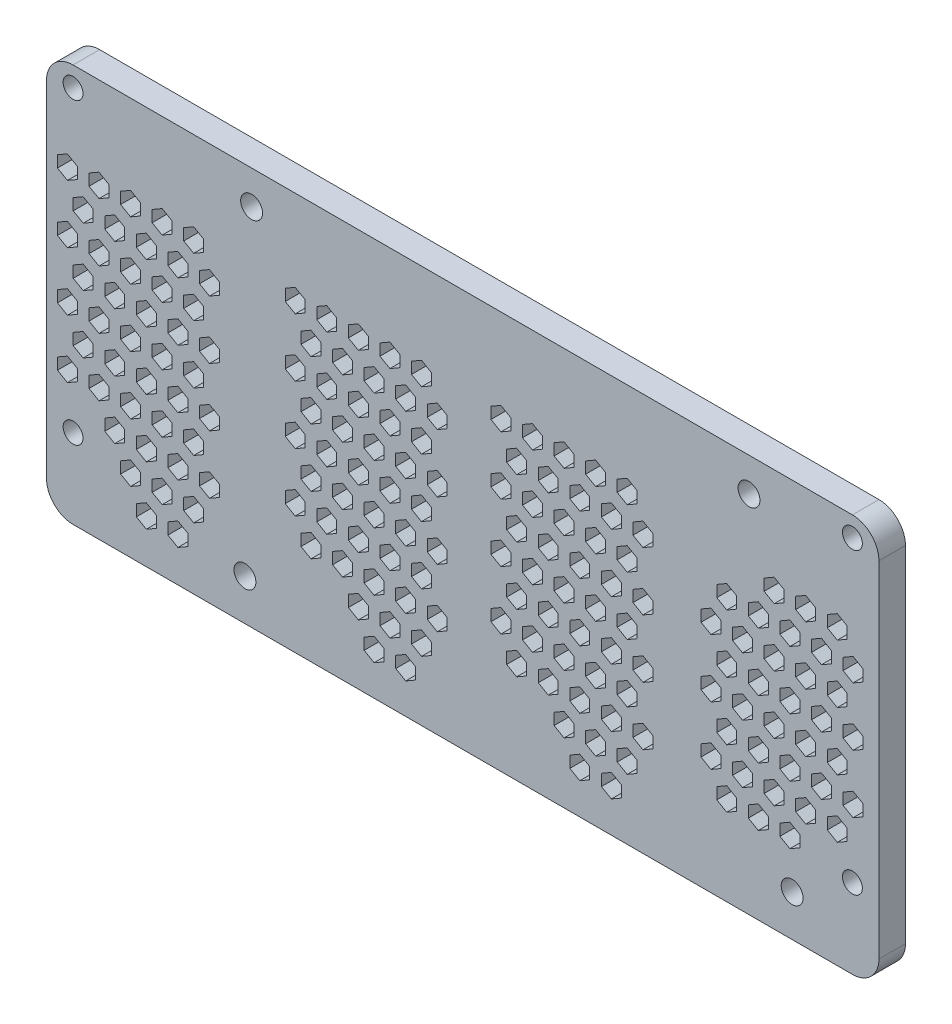
SolidWorks part; units mm, degrees
ref_plane "Front Plane" through (0, 0, 0) normal (0, 0, 1) x (1, 0, 0)
ref_plane "Top Plane" through (0, 0, 0) normal (0, 1, 0) x (1, 0, 0)
ref_plane "Right Plane" through (0, 0, 0) normal (1, 0, 0) x (0, 0, -1)
sketch "Sketch1" plane through (0, 0, 0) normal (0, 0, 1) x (1, 0, 0)
  line L1 (-44, 25.5882) -> (73.5, 25.5882)
  line L2 (-48, 21.5882) -> (-48, -30.4118)
  line L3 (-44, -34.4118) -> (73.5, -34.4118)
  line L4 (77.5, 21.5882) -> (77.5, -30.4118)
  line L10 (-44.8542, 13.5468) -> (-46.3542, 12.6808)
  line L11 (-46.3542, 12.6808) -> (-46.3542, 10.9488)
  line L12 (-46.3542, 10.9488) -> (-44.8542, 10.0827)
  line L13 (-44.8542, 10.0827) -> (-43.3542, 10.9488)
  line L14 (-43.3542, 10.9488) -> (-43.3542, 12.6808)
  line L15 (-43.3542, 12.6808) -> (-44.8542, 13.5468)
  line L17 (-42.4786, 9.1449) -> (-43.9786, 8.2789)
  line L18 (-43.9786, 8.2789) -> (-43.9786, 6.5468)
  line L19 (-43.9786, 6.5468) -> (-42.4786, 5.6808)
  line L20 (-42.4786, 5.6808) -> (-40.9786, 6.5468)
  line L21 (-40.9786, 6.5468) -> (-40.9786, 8.2789)
  line L22 (-40.9786, 8.2789) -> (-42.4786, 9.1449)
  line L23 (-40.0942, 13.5468) -> (-41.5942, 12.6808)
  line L24 (-41.5942, 12.6808) -> (-41.5942, 10.9488)
  line L25 (-41.5942, 10.9488) -> (-40.0942, 10.0827)
  line L26 (-40.0942, 10.0827) -> (-38.5942, 10.9488)
  line L27 (-38.5942, 10.9488) -> (-38.5942, 12.6808)
  line L28 (-38.5942, 12.6808) -> (-40.0942, 13.5468)
  line L29 (-37.7186, 9.1449) -> (-39.2186, 8.2789)
  line L30 (-39.2186, 8.2789) -> (-39.2186, 6.5468)
  line L31 (-39.2186, 6.5468) -> (-37.7186, 5.6808)
  line L32 (-37.7186, 5.6808) -> (-36.2186, 6.5468)
  line L33 (-36.2186, 6.5468) -> (-36.2186, 8.2789)
  line L34 (-36.2186, 8.2789) -> (-37.7186, 9.1449)
  line L35 (-35.3342, 13.5468) -> (-36.8342, 12.6808)
  line L36 (-36.8342, 12.6808) -> (-36.8342, 10.9488)
  line L37 (-36.8342, 10.9488) -> (-35.3342, 10.0827)
  line L38 (-35.3342, 10.0827) -> (-33.8342, 10.9488)
  line L39 (-33.8342, 10.9488) -> (-33.8342, 12.6808)
  line L40 (-33.8342, 12.6808) -> (-35.3342, 13.5468)
  line L41 (-32.9586, 9.1449) -> (-34.4586, 8.2789)
  line L42 (-34.4586, 8.2789) -> (-34.4586, 6.5468)
  line L43 (-34.4586, 6.5468) -> (-32.9586, 5.6808)
  line L44 (-32.9586, 5.6808) -> (-31.4586, 6.5468)
  line L45 (-31.4586, 6.5468) -> (-31.4586, 8.2789)
  line L46 (-31.4586, 8.2789) -> (-32.9586, 9.1449)
  line L47 (-30.5742, 13.5468) -> (-32.0742, 12.6808)
  line L48 (-32.0742, 12.6808) -> (-32.0742, 10.9488)
  line L49 (-32.0742, 10.9488) -> (-30.5742, 10.0827)
  line L50 (-30.5742, 10.0827) -> (-29.0742, 10.9488)
  line L51 (-29.0742, 10.9488) -> (-29.0742, 12.6808)
  line L52 (-29.0742, 12.6808) -> (-30.5742, 13.5468)
  line L53 (-28.1986, 9.1449) -> (-29.6986, 8.2789)
  line L54 (-29.6986, 8.2789) -> (-29.6986, 6.5468)
  line L55 (-29.6986, 6.5468) -> (-28.1986, 5.6808)
  line L56 (-28.1986, 5.6808) -> (-26.6986, 6.5468)
  line L57 (-26.6986, 6.5468) -> (-26.6986, 8.2789)
  line L58 (-26.6986, 8.2789) -> (-28.1986, 9.1449)
  line L59 (-25.8142, 13.5468) -> (-27.3142, 12.6808)
  line L60 (-27.3142, 12.6808) -> (-27.3142, 10.9488)
  line L61 (-27.3142, 10.9488) -> (-25.8142, 10.0827)
  line L62 (-25.8142, 10.0827) -> (-24.3142, 10.9488)
  line L63 (-24.3142, 10.9488) -> (-24.3142, 12.6808)
  line L64 (-24.3142, 12.6808) -> (-25.8142, 13.5468)
  line L65 (-23.4386, 9.1449) -> (-24.9386, 8.2789)
  line L66 (-24.9386, 8.2789) -> (-24.9386, 6.5468)
  line L67 (-24.9386, 6.5468) -> (-23.4386, 5.6808)
  line L68 (-23.4386, 5.6808) -> (-21.9386, 6.5468)
  line L69 (-21.9386, 6.5468) -> (-21.9386, 8.2789)
  line L70 (-21.9386, 8.2789) -> (-23.4386, 9.1449)
  line L71 (-40.0942, 4.7468) -> (-41.5942, 3.8808)
  line L72 (-41.5942, 3.8808) -> (-41.5942, 2.1488)
  line L73 (-41.5942, 2.1488) -> (-40.0942, 1.2827)
  line L74 (-40.0942, 1.2827) -> (-38.5942, 2.1488)
  line L75 (-38.5942, 2.1488) -> (-38.5942, 3.8808)
  line L76 (-38.5942, 3.8808) -> (-40.0942, 4.7468)
  line L77 (-37.7186, 0.3449) -> (-39.2186, -0.5211)
  line L78 (-39.2186, -0.5211) -> (-39.2186, -2.2532)
  line L79 (-39.2186, -2.2532) -> (-37.7186, -3.1192)
  line L80 (-37.7186, -3.1192) -> (-36.2186, -2.2532)
  line L81 (-36.2186, -2.2532) -> (-36.2186, -0.5211)
  line L82 (-36.2186, -0.5211) -> (-37.7186, 0.3449)
  line L83 (-35.3342, 4.7468) -> (-36.8342, 3.8808)
  line L84 (-36.8342, 3.8808) -> (-36.8342, 2.1488)
  line L85 (-36.8342, 2.1488) -> (-35.3342, 1.2827)
  line L86 (-35.3342, 1.2827) -> (-33.8342, 2.1488)
  line L87 (-33.8342, 2.1488) -> (-33.8342, 3.8808)
  line L88 (-33.8342, 3.8808) -> (-35.3342, 4.7468)
  line L89 (-32.9586, 0.3449) -> (-34.4586, -0.5211)
  line L90 (-34.4586, -0.5211) -> (-34.4586, -2.2532)
  line L91 (-34.4586, -2.2532) -> (-32.9586, -3.1192)
  line L92 (-32.9586, -3.1192) -> (-31.4586, -2.2532)
  line L93 (-31.4586, -2.2532) -> (-31.4586, -0.5211)
  line L94 (-31.4586, -0.5211) -> (-32.9586, 0.3449)
  line L95 (-30.5742, 4.7468) -> (-32.0742, 3.8808)
  line L96 (-32.0742, 3.8808) -> (-32.0742, 2.1488)
  line L97 (-32.0742, 2.1488) -> (-30.5742, 1.2827)
  line L98 (-30.5742, 1.2827) -> (-29.0742, 2.1488)
  line L99 (-29.0742, 2.1488) -> (-29.0742, 3.8808)
  line L100 (-29.0742, 3.8808) -> (-30.5742, 4.7468)
  line L101 (-28.1986, 0.3449) -> (-29.6986, -0.5211)
  line L102 (-29.6986, -0.5211) -> (-29.6986, -2.2532)
  line L103 (-29.6986, -2.2532) -> (-28.1986, -3.1192)
  line L104 (-28.1986, -3.1192) -> (-26.6986, -2.2532)
  line L105 (-26.6986, -2.2532) -> (-26.6986, -0.5211)
  line L106 (-26.6986, -0.5211) -> (-28.1986, 0.3449)
  line L107 (-25.8142, 4.7468) -> (-27.3142, 3.8808)
  line L108 (-27.3142, 3.8808) -> (-27.3142, 2.1488)
  line L109 (-27.3142, 2.1488) -> (-25.8142, 1.2827)
  line L110 (-25.8142, 1.2827) -> (-24.3142, 2.1488)
  line L111 (-24.3142, 2.1488) -> (-24.3142, 3.8808)
  line L112 (-24.3142, 3.8808) -> (-25.8142, 4.7468)
  line L113 (-23.4386, 0.3449) -> (-24.9386, -0.5211)
  line L114 (-24.9386, -0.5211) -> (-24.9386, -2.2532)
  line L115 (-24.9386, -2.2532) -> (-23.4386, -3.1192)
  line L116 (-23.4386, -3.1192) -> (-21.9386, -2.2532)
  line L117 (-21.9386, -2.2532) -> (-21.9386, -0.5211)
  line L118 (-21.9386, -0.5211) -> (-23.4386, 0.3449)
  line L119 (-40.0942, -4.0532) -> (-41.5942, -4.9192)
  line L120 (-41.5942, -4.9192) -> (-41.5942, -6.6512)
  line L121 (-41.5942, -6.6512) -> (-40.0942, -7.5173)
  line L122 (-40.0942, -7.5173) -> (-38.5942, -6.6512)
  line L123 (-38.5942, -6.6512) -> (-38.5942, -4.9192)
  line L124 (-38.5942, -4.9192) -> (-40.0942, -4.0532)
  line L125 (-37.7186, -8.4551) -> (-39.2186, -9.3211)
  line L126 (-39.2186, -9.3211) -> (-39.2186, -11.0532)
  line L127 (-39.2186, -11.0532) -> (-37.7186, -11.9192)
  line L128 (-37.7186, -11.9192) -> (-36.2186, -11.0532)
  line L129 (-36.2186, -11.0532) -> (-36.2186, -9.3211)
  line L130 (-36.2186, -9.3211) -> (-37.7186, -8.4551)
  line L131 (-35.3342, -4.0532) -> (-36.8342, -4.9192)
  line L132 (-36.8342, -4.9192) -> (-36.8342, -6.6512)
  line L133 (-36.8342, -6.6512) -> (-35.3342, -7.5173)
  line L134 (-35.3342, -7.5173) -> (-33.8342, -6.6512)
  line L135 (-33.8342, -6.6512) -> (-33.8342, -4.9192)
  line L136 (-33.8342, -4.9192) -> (-35.3342, -4.0532)
  line L137 (-32.9586, -8.4551) -> (-34.4586, -9.3211)
  line L138 (-34.4586, -9.3211) -> (-34.4586, -11.0532)
  line L139 (-34.4586, -11.0532) -> (-32.9586, -11.9192)
  line L140 (-32.9586, -11.9192) -> (-31.4586, -11.0532)
  line L141 (-31.4586, -11.0532) -> (-31.4586, -9.3211)
  line L142 (-31.4586, -9.3211) -> (-32.9586, -8.4551)
  line L143 (-30.5742, -4.0532) -> (-32.0742, -4.9192)
  line L144 (-32.0742, -4.9192) -> (-32.0742, -6.6512)
  line L145 (-32.0742, -6.6512) -> (-30.5742, -7.5173)
  line L146 (-30.5742, -7.5173) -> (-29.0742, -6.6512)
  line L147 (-29.0742, -6.6512) -> (-29.0742, -4.9192)
  line L148 (-29.0742, -4.9192) -> (-30.5742, -4.0532)
  line L149 (-28.1986, -8.4551) -> (-29.6986, -9.3211)
  line L150 (-29.6986, -9.3211) -> (-29.6986, -11.0532)
  line L151 (-29.6986, -11.0532) -> (-28.1986, -11.9192)
  line L152 (-28.1986, -11.9192) -> (-26.6986, -11.0532)
  line L153 (-26.6986, -11.0532) -> (-26.6986, -9.3211)
  line L154 (-26.6986, -9.3211) -> (-28.1986, -8.4551)
  line L155 (-25.8142, -4.0532) -> (-27.3142, -4.9192)
  line L156 (-27.3142, -4.9192) -> (-27.3142, -6.6512)
  line L157 (-27.3142, -6.6512) -> (-25.8142, -7.5173)
  line L158 (-25.8142, -7.5173) -> (-24.3142, -6.6512)
  line L159 (-24.3142, -6.6512) -> (-24.3142, -4.9192)
  line L160 (-24.3142, -4.9192) -> (-25.8142, -4.0532)
  line L161 (-23.4386, -8.4551) -> (-24.9386, -9.3211)
  line L162 (-24.9386, -9.3211) -> (-24.9386, -11.0532)
  line L163 (-24.9386, -11.0532) -> (-23.4386, -11.9192)
  line L164 (-23.4386, -11.9192) -> (-21.9386, -11.0532)
  line L165 (-21.9386, -11.0532) -> (-21.9386, -9.3211)
  line L166 (-21.9386, -9.3211) -> (-23.4386, -8.4551)
  line L167 (-40.0942, -12.8532) -> (-41.5942, -13.7192)
  line L168 (-41.5942, -13.7192) -> (-41.5942, -15.4512)
  line L169 (-41.5942, -15.4512) -> (-40.0942, -16.3173)
  line L170 (-40.0942, -16.3173) -> (-38.5942, -15.4512)
  line L171 (-38.5942, -15.4512) -> (-38.5942, -13.7192)
  line L172 (-38.5942, -13.7192) -> (-40.0942, -12.8532)
  line L173 (-37.7186, -17.2551) -> (-39.2186, -18.1211)
  line L174 (-39.2186, -18.1211) -> (-39.2186, -19.8532)
  line L175 (-39.2186, -19.8532) -> (-37.7186, -20.7192)
  line L176 (-37.7186, -20.7192) -> (-36.2186, -19.8532)
  line L177 (-36.2186, -19.8532) -> (-36.2186, -18.1211)
  line L178 (-36.2186, -18.1211) -> (-37.7186, -17.2551)
  line L179 (-35.3342, -12.8532) -> (-36.8342, -13.7192)
  line L180 (-36.8342, -13.7192) -> (-36.8342, -15.4512)
  line L181 (-36.8342, -15.4512) -> (-35.3342, -16.3173)
  line L182 (-35.3342, -16.3173) -> (-33.8342, -15.4512)
  line L183 (-33.8342, -15.4512) -> (-33.8342, -13.7192)
  line L184 (-33.8342, -13.7192) -> (-35.3342, -12.8532)
  line L185 (-32.9586, -17.2551) -> (-34.4586, -18.1211)
  line L186 (-34.4586, -18.1211) -> (-34.4586, -19.8532)
  line L187 (-34.4586, -19.8532) -> (-32.9586, -20.7192)
  line L188 (-32.9586, -20.7192) -> (-31.4586, -19.8532)
  line L189 (-31.4586, -19.8532) -> (-31.4586, -18.1211)
  line L190 (-31.4586, -18.1211) -> (-32.9586, -17.2551)
  line L191 (-30.5742, -12.8532) -> (-32.0742, -13.7192)
  line L192 (-32.0742, -13.7192) -> (-32.0742, -15.4512)
  line L193 (-32.0742, -15.4512) -> (-30.5742, -16.3173)
  line L194 (-30.5742, -16.3173) -> (-29.0742, -15.4512)
  line L195 (-29.0742, -15.4512) -> (-29.0742, -13.7192)
  line L196 (-29.0742, -13.7192) -> (-30.5742, -12.8532)
  line L197 (-28.1986, -17.2551) -> (-29.6986, -18.1211)
  line L198 (-29.6986, -18.1211) -> (-29.6986, -19.8532)
  line L199 (-29.6986, -19.8532) -> (-28.1986, -20.7192)
  line L200 (-28.1986, -20.7192) -> (-26.6986, -19.8532)
  line L201 (-26.6986, -19.8532) -> (-26.6986, -18.1211)
  line L202 (-26.6986, -18.1211) -> (-28.1986, -17.2551)
  line L203 (-25.8142, -12.8532) -> (-27.3142, -13.7192)
  line L204 (-27.3142, -13.7192) -> (-27.3142, -15.4512)
  line L205 (-27.3142, -15.4512) -> (-25.8142, -16.3173)
  line L206 (-25.8142, -16.3173) -> (-24.3142, -15.4512)
  line L207 (-24.3142, -15.4512) -> (-24.3142, -13.7192)
  line L208 (-24.3142, -13.7192) -> (-25.8142, -12.8532)
  line L209 (-23.4386, -17.2551) -> (-24.9386, -18.1211)
  line L210 (-24.9386, -18.1211) -> (-24.9386, -19.8532)
  line L211 (-24.9386, -19.8532) -> (-23.4386, -20.7192)
  line L212 (-23.4386, -20.7192) -> (-21.9386, -19.8532)
  line L213 (-21.9386, -19.8532) -> (-21.9386, -18.1211)
  line L214 (-21.9386, -18.1211) -> (-23.4386, -17.2551)
  line L227 (-35.3342, -21.6532) -> (-36.8342, -22.5192)
  line L228 (-36.8342, -22.5192) -> (-36.8342, -24.2512)
  line L229 (-36.8342, -24.2512) -> (-35.3342, -25.1173)
  line L230 (-35.3342, -25.1173) -> (-33.8342, -24.2512)
  line L231 (-33.8342, -24.2512) -> (-33.8342, -22.5192)
  line L232 (-33.8342, -22.5192) -> (-35.3342, -21.6532)
  line L233 (-32.9586, -26.0551) -> (-34.4586, -26.9211)
  line L234 (-34.4586, -26.9211) -> (-34.4586, -28.6532)
  line L235 (-34.4586, -28.6532) -> (-32.9586, -29.5192)
  line L236 (-32.9586, -29.5192) -> (-31.4586, -28.6532)
  line L237 (-31.4586, -28.6532) -> (-31.4586, -26.9211)
  line L238 (-31.4586, -26.9211) -> (-32.9586, -26.0551)
  line L239 (-30.5742, -21.6532) -> (-32.0742, -22.5192)
  line L240 (-32.0742, -22.5192) -> (-32.0742, -24.2512)
  line L241 (-32.0742, -24.2512) -> (-30.5742, -25.1173)
  line L242 (-30.5742, -25.1173) -> (-29.0742, -24.2512)
  line L243 (-29.0742, -24.2512) -> (-29.0742, -22.5192)
  line L244 (-29.0742, -22.5192) -> (-30.5742, -21.6532)
  line L245 (-28.1986, -26.0551) -> (-29.6986, -26.9211)
  line L246 (-29.6986, -26.9211) -> (-29.6986, -28.6532)
  line L247 (-29.6986, -28.6532) -> (-28.1986, -29.5192)
  line L248 (-28.1986, -29.5192) -> (-26.6986, -28.6532)
  line L249 (-26.6986, -28.6532) -> (-26.6986, -26.9211)
  line L250 (-26.6986, -26.9211) -> (-28.1986, -26.0551)
  line L251 (-25.8142, -21.6532) -> (-27.3142, -22.5192)
  line L252 (-27.3142, -22.5192) -> (-27.3142, -24.2512)
  line L253 (-27.3142, -24.2512) -> (-25.8142, -25.1173)
  line L254 (-25.8142, -25.1173) -> (-24.3142, -24.2512)
  line L255 (-24.3142, -24.2512) -> (-24.3142, -22.5192)
  line L256 (-24.3142, -22.5192) -> (-25.8142, -21.6532)
  line L263 (-44.8542, 4.7468) -> (-46.3542, 3.8808)
  line L264 (-46.3542, 3.8808) -> (-46.3542, 2.1488)
  line L265 (-46.3542, 2.1488) -> (-44.8542, 1.2827)
  line L266 (-44.8542, 1.2827) -> (-43.3542, 2.1488)
  line L267 (-43.3542, 2.1488) -> (-43.3542, 3.8808)
  line L268 (-43.3542, 3.8808) -> (-44.8542, 4.7468)
  line L269 (-42.4786, 0.3449) -> (-43.9786, -0.5211)
  line L270 (-43.9786, -0.5211) -> (-43.9786, -2.2532)
  line L271 (-43.9786, -2.2532) -> (-42.4786, -3.1192)
  line L272 (-42.4786, -3.1192) -> (-40.9786, -2.2532)
  line L273 (-40.9786, -2.2532) -> (-40.9786, -0.5211)
  line L274 (-40.9786, -0.5211) -> (-42.4786, 0.3449)
  line L275 (-44.8542, -4.0532) -> (-46.3542, -4.9192)
  line L276 (-46.3542, -4.9192) -> (-46.3542, -6.6512)
  line L277 (-46.3542, -6.6512) -> (-44.8542, -7.5173)
  line L278 (-44.8542, -7.5173) -> (-43.3542, -6.6512)
  line L279 (-43.3542, -6.6512) -> (-43.3542, -4.9192)
  line L280 (-43.3542, -4.9192) -> (-44.8542, -4.0532)
  line L281 (-42.4786, -8.4551) -> (-43.9786, -9.3211)
  line L282 (-43.9786, -9.3211) -> (-43.9786, -11.0532)
  line L283 (-43.9786, -11.0532) -> (-42.4786, -11.9192)
  line L284 (-42.4786, -11.9192) -> (-40.9786, -11.0532)
  line L285 (-40.9786, -11.0532) -> (-40.9786, -9.3211)
  line L286 (-40.9786, -9.3211) -> (-42.4786, -8.4551)
  line L287 (-44.8542, -12.8532) -> (-46.3542, -13.7192)
  line L288 (-46.3542, -13.7192) -> (-46.3542, -15.4512)
  line L289 (-46.3542, -15.4512) -> (-44.8542, -16.3173)
  line L290 (-44.8542, -16.3173) -> (-43.3542, -15.4512)
  line L291 (-43.3542, -15.4512) -> (-43.3542, -13.7192)
  line L292 (-43.3542, -13.7192) -> (-44.8542, -12.8532)
  line L311 (-44.8542, -21.6532) -> (-46.3542, -22.5192) [skipped]
  line L312 (-46.3542, -22.5192) -> (-46.3542, -24.2512) [skipped]
  line L313 (-46.3542, -24.2512) -> (-44.8542, -25.1173) [skipped]
  line L314 (-44.8542, -25.1173) -> (-43.3542, -24.2512) [skipped]
  line L315 (-43.3542, -24.2512) -> (-43.3542, -22.5192) [skipped]
  line L316 (-43.3542, -22.5192) -> (-44.8542, -21.6532) [skipped]
  line L317 (-42.4786, -26.0551) -> (-43.9786, -26.9211) [skipped]
  line L318 (-43.9786, -26.9211) -> (-43.9786, -28.6532) [skipped]
  line L319 (-43.9786, -28.6532) -> (-42.4786, -29.5192) [skipped]
  line L320 (-42.4786, -29.5192) -> (-40.9786, -28.6532) [skipped]
  line L321 (-40.9786, -28.6532) -> (-40.9786, -26.9211) [skipped]
  line L322 (-40.9786, -26.9211) -> (-42.4786, -26.0551) [skipped]
  line L323 (-37.7186, -26.0551) -> (-39.2186, -26.9211) [skipped]
  line L324 (-39.2186, -26.9211) -> (-39.2186, -28.6532) [skipped]
  line L325 (-39.2186, -28.6532) -> (-37.7186, -29.5192) [skipped]
  line L326 (-37.7186, -29.5192) -> (-36.2186, -28.6532) [skipped]
  line L327 (-36.2186, -28.6532) -> (-36.2186, -26.9211) [skipped]
  line L328 (-36.2186, -26.9211) -> (-37.7186, -26.0551) [skipped]
  line L329 (-40.0942, -21.6532) -> (-41.5942, -22.5192) [skipped]
  line L330 (-41.5942, -22.5192) -> (-41.5942, -24.2512) [skipped]
  line L331 (-41.5942, -24.2512) -> (-40.0942, -25.1173) [skipped]
  line L332 (-40.0942, -25.1173) -> (-38.5942, -24.2512) [skipped]
  line L333 (-38.5942, -24.2512) -> (-38.5942, -22.5192) [skipped]
  line L334 (-38.5942, -22.5192) -> (-40.0942, -21.6532) [skipped]
  line L335 (-23.4386, -26.0551) -> (-24.9386, -26.9211) [skipped]
  line L336 (-24.9386, -26.9211) -> (-24.9386, -28.6532) [skipped]
  line L337 (-24.9386, -28.6532) -> (-23.4386, -29.5192) [skipped]
  line L338 (-23.4386, -29.5192) -> (-21.9386, -28.6532) [skipped]
  line L339 (-21.9386, -28.6532) -> (-21.9386, -26.9211) [skipped]
  line L340 (-21.9386, -26.9211) -> (-23.4386, -26.0551) [skipped]
  line L347 (54.5534, 7.152) -> (53.0534, 6.286)
  line L348 (53.0534, 6.286) -> (53.0534, 4.554)
  line L349 (53.0534, 4.554) -> (54.5534, 3.6879)
  line L350 (54.5534, 3.6879) -> (56.0534, 4.554)
  line L351 (56.0534, 4.554) -> (56.0534, 6.286)
  line L352 (56.0534, 6.286) -> (54.5534, 7.152)
  line L359 (59.3134, 7.152) -> (57.8134, 6.286)
  line L360 (57.8134, 6.286) -> (57.8134, 4.554)
  line L361 (57.8134, 4.554) -> (59.3134, 3.6879)
  line L362 (59.3134, 3.6879) -> (60.8134, 4.554)
  line L363 (60.8134, 4.554) -> (60.8134, 6.286)
  line L364 (60.8134, 6.286) -> (59.3134, 7.152)
  line L365 (61.6978, 11.554) -> (60.1978, 10.6879)
  line L366 (60.1978, 10.6879) -> (60.1978, 8.9559)
  line L367 (60.1978, 8.9559) -> (61.6978, 8.0899)
  line L368 (61.6978, 8.0899) -> (63.1978, 8.9559)
  line L369 (63.1978, 8.9559) -> (63.1978, 10.6879)
  line L370 (63.1978, 10.6879) -> (61.6978, 11.554)
  line L371 (64.0734, 7.152) -> (62.5734, 6.286)
  line L372 (62.5734, 6.286) -> (62.5734, 4.554)
  line L373 (62.5734, 4.554) -> (64.0734, 3.6879)
  line L374 (64.0734, 3.6879) -> (65.5734, 4.554)
  line L375 (65.5734, 4.554) -> (65.5734, 6.286)
  line L376 (65.5734, 6.286) -> (64.0734, 7.152)
  line L377 (66.4578, 11.554) -> (64.9578, 10.6879)
  line L378 (64.9578, 10.6879) -> (64.9578, 8.9559)
  line L379 (64.9578, 8.9559) -> (66.4578, 8.0899)
  line L380 (66.4578, 8.0899) -> (67.9578, 8.9559)
  line L381 (67.9578, 8.9559) -> (67.9578, 10.6879)
  line L382 (67.9578, 10.6879) -> (66.4578, 11.554)
  line L383 (68.8334, 7.152) -> (67.3334, 6.286)
  line L384 (67.3334, 6.286) -> (67.3334, 4.554)
  line L385 (67.3334, 4.554) -> (68.8334, 3.6879)
  line L386 (68.8334, 3.6879) -> (70.3334, 4.554)
  line L387 (70.3334, 4.554) -> (70.3334, 6.286)
  line L388 (70.3334, 6.286) -> (68.8334, 7.152)
  line L389 (71.2178, 11.554) -> (69.7178, 10.6879)
  line L390 (69.7178, 10.6879) -> (69.7178, 8.9559)
  line L391 (69.7178, 8.9559) -> (71.2178, 8.0899)
  line L392 (71.2178, 8.0899) -> (72.7178, 8.9559)
  line L393 (72.7178, 8.9559) -> (72.7178, 10.6879)
  line L394 (72.7178, 10.6879) -> (71.2178, 11.554)
  line L395 (73.5934, 7.152) -> (72.0934, 6.286)
  line L396 (72.0934, 6.286) -> (72.0934, 4.554)
  line L397 (72.0934, 4.554) -> (73.5934, 3.6879)
  line L398 (73.5934, 3.6879) -> (75.0934, 4.554)
  line L399 (75.0934, 4.554) -> (75.0934, 6.286)
  line L400 (75.0934, 6.286) -> (73.5934, 7.152)
  line L401 (56.9378, 2.754) -> (55.4378, 1.8879)
  line L402 (55.4378, 1.8879) -> (55.4378, 0.1559)
  line L403 (55.4378, 0.1559) -> (56.9378, -0.7101)
  line L404 (56.9378, -0.7101) -> (58.4378, 0.1559)
  line L405 (58.4378, 0.1559) -> (58.4378, 1.8879)
  line L406 (58.4378, 1.8879) -> (56.9378, 2.754)
  line L407 (59.3134, -1.648) -> (57.8134, -2.514)
  line L408 (57.8134, -2.514) -> (57.8134, -4.246)
  line L409 (57.8134, -4.246) -> (59.3134, -5.1121)
  line L410 (59.3134, -5.1121) -> (60.8134, -4.246)
  line L411 (60.8134, -4.246) -> (60.8134, -2.514)
  line L412 (60.8134, -2.514) -> (59.3134, -1.648)
  line L413 (61.6978, 2.754) -> (60.1978, 1.8879)
  line L414 (60.1978, 1.8879) -> (60.1978, 0.1559)
  line L415 (60.1978, 0.1559) -> (61.6978, -0.7101)
  line L416 (61.6978, -0.7101) -> (63.1978, 0.1559)
  line L417 (63.1978, 0.1559) -> (63.1978, 1.8879)
  line L418 (63.1978, 1.8879) -> (61.6978, 2.754)
  line L419 (64.0734, -1.648) -> (62.5734, -2.514)
  line L420 (62.5734, -2.514) -> (62.5734, -4.246)
  line L421 (62.5734, -4.246) -> (64.0734, -5.1121)
  line L422 (64.0734, -5.1121) -> (65.5734, -4.246)
  line L423 (65.5734, -4.246) -> (65.5734, -2.514)
  line L424 (65.5734, -2.514) -> (64.0734, -1.648)
  line L425 (66.4578, 2.754) -> (64.9578, 1.8879)
  line L426 (64.9578, 1.8879) -> (64.9578, 0.1559)
  line L427 (64.9578, 0.1559) -> (66.4578, -0.7101)
  line L428 (66.4578, -0.7101) -> (67.9578, 0.1559)
  line L429 (67.9578, 0.1559) -> (67.9578, 1.8879)
  line L430 (67.9578, 1.8879) -> (66.4578, 2.754)
  line L431 (68.8334, -1.648) -> (67.3334, -2.514)
  line L432 (67.3334, -2.514) -> (67.3334, -4.246)
  line L433 (67.3334, -4.246) -> (68.8334, -5.1121)
  line L434 (68.8334, -5.1121) -> (70.3334, -4.246)
  line L435 (70.3334, -4.246) -> (70.3334, -2.514)
  line L436 (70.3334, -2.514) -> (68.8334, -1.648)
  line L437 (71.2178, 2.754) -> (69.7178, 1.8879)
  line L438 (69.7178, 1.8879) -> (69.7178, 0.1559)
  line L439 (69.7178, 0.1559) -> (71.2178, -0.7101)
  line L440 (71.2178, -0.7101) -> (72.7178, 0.1559)
  line L441 (72.7178, 0.1559) -> (72.7178, 1.8879)
  line L442 (72.7178, 1.8879) -> (71.2178, 2.754)
  line L443 (73.5934, -1.648) -> (72.0934, -2.514)
  line L444 (72.0934, -2.514) -> (72.0934, -4.246)
  line L445 (72.0934, -4.246) -> (73.5934, -5.1121)
  line L446 (73.5934, -5.1121) -> (75.0934, -4.246)
  line L447 (75.0934, -4.246) -> (75.0934, -2.514)
  line L448 (75.0934, -2.514) -> (73.5934, -1.648)
  line L449 (56.9378, -6.046) -> (55.4378, -6.9121)
  line L450 (55.4378, -6.9121) -> (55.4378, -8.6441)
  line L451 (55.4378, -8.6441) -> (56.9378, -9.5101)
  line L452 (56.9378, -9.5101) -> (58.4378, -8.6441)
  line L453 (58.4378, -8.6441) -> (58.4378, -6.9121)
  line L454 (58.4378, -6.9121) -> (56.9378, -6.046)
  line L455 (59.3134, -10.448) -> (57.8134, -11.314)
  line L456 (57.8134, -11.314) -> (57.8134, -13.046)
  line L457 (57.8134, -13.046) -> (59.3134, -13.9121)
  line L458 (59.3134, -13.9121) -> (60.8134, -13.046)
  line L459 (60.8134, -13.046) -> (60.8134, -11.314)
  line L460 (60.8134, -11.314) -> (59.3134, -10.448)
  line L461 (61.6978, -6.046) -> (60.1978, -6.9121)
  line L462 (60.1978, -6.9121) -> (60.1978, -8.6441)
  line L463 (60.1978, -8.6441) -> (61.6978, -9.5101)
  line L464 (61.6978, -9.5101) -> (63.1978, -8.6441)
  line L465 (63.1978, -8.6441) -> (63.1978, -6.9121)
  line L466 (63.1978, -6.9121) -> (61.6978, -6.046)
  line L467 (64.0734, -10.448) -> (62.5734, -11.314)
  line L468 (62.5734, -11.314) -> (62.5734, -13.046)
  line L469 (62.5734, -13.046) -> (64.0734, -13.9121)
  line L470 (64.0734, -13.9121) -> (65.5734, -13.046)
  line L471 (65.5734, -13.046) -> (65.5734, -11.314)
  line L472 (65.5734, -11.314) -> (64.0734, -10.448)
  line L473 (66.4578, -6.046) -> (64.9578, -6.9121)
  line L474 (64.9578, -6.9121) -> (64.9578, -8.6441)
  line L475 (64.9578, -8.6441) -> (66.4578, -9.5101)
  line L476 (66.4578, -9.5101) -> (67.9578, -8.6441)
  line L477 (67.9578, -8.6441) -> (67.9578, -6.9121)
  line L478 (67.9578, -6.9121) -> (66.4578, -6.046)
  line L479 (68.8334, -10.448) -> (67.3334, -11.314)
  line L480 (67.3334, -11.314) -> (67.3334, -13.046)
  line L481 (67.3334, -13.046) -> (68.8334, -13.9121)
  line L482 (68.8334, -13.9121) -> (70.3334, -13.046)
  line L483 (70.3334, -13.046) -> (70.3334, -11.314)
  line L484 (70.3334, -11.314) -> (68.8334, -10.448)
  line L485 (71.2178, -6.046) -> (69.7178, -6.9121)
  line L486 (69.7178, -6.9121) -> (69.7178, -8.6441)
  line L487 (69.7178, -8.6441) -> (71.2178, -9.5101)
  line L488 (71.2178, -9.5101) -> (72.7178, -8.6441)
  line L489 (72.7178, -8.6441) -> (72.7178, -6.9121)
  line L490 (72.7178, -6.9121) -> (71.2178, -6.046)
  line L491 (73.5934, -10.448) -> (72.0934, -11.314)
  line L492 (72.0934, -11.314) -> (72.0934, -13.046)
  line L493 (72.0934, -13.046) -> (73.5934, -13.9121)
  line L494 (73.5934, -13.9121) -> (75.0934, -13.046)
  line L495 (75.0934, -13.046) -> (75.0934, -11.314)
  line L496 (75.0934, -11.314) -> (73.5934, -10.448)
  line L497 (56.9378, -14.846) -> (55.4378, -15.7121)
  line L498 (55.4378, -15.7121) -> (55.4378, -17.4441)
  line L499 (55.4378, -17.4441) -> (56.9378, -18.3101)
  line L500 (56.9378, -18.3101) -> (58.4378, -17.4441)
  line L501 (58.4378, -17.4441) -> (58.4378, -15.7121)
  line L502 (58.4378, -15.7121) -> (56.9378, -14.846)
  line L503 (59.3134, -19.248) -> (57.8134, -20.114)
  line L504 (57.8134, -20.114) -> (57.8134, -21.846)
  line L505 (57.8134, -21.846) -> (59.3134, -22.7121)
  line L506 (59.3134, -22.7121) -> (60.8134, -21.846)
  line L507 (60.8134, -21.846) -> (60.8134, -20.114)
  line L508 (60.8134, -20.114) -> (59.3134, -19.248)
  line L509 (61.6978, -14.846) -> (60.1978, -15.7121)
  line L510 (60.1978, -15.7121) -> (60.1978, -17.4441)
  line L511 (60.1978, -17.4441) -> (61.6978, -18.3101)
  line L512 (61.6978, -18.3101) -> (63.1978, -17.4441)
  line L513 (63.1978, -17.4441) -> (63.1978, -15.7121)
  line L514 (63.1978, -15.7121) -> (61.6978, -14.846)
  line L515 (64.0734, -19.248) -> (62.5734, -20.114)
  line L516 (62.5734, -20.114) -> (62.5734, -21.846)
  line L517 (62.5734, -21.846) -> (64.0734, -22.7121)
  line L518 (64.0734, -22.7121) -> (65.5734, -21.846)
  line L519 (65.5734, -21.846) -> (65.5734, -20.114)
  line L520 (65.5734, -20.114) -> (64.0734, -19.248)
  line L521 (66.4578, -14.846) -> (64.9578, -15.7121)
  line L522 (64.9578, -15.7121) -> (64.9578, -17.4441)
  line L523 (64.9578, -17.4441) -> (66.4578, -18.3101)
  line L524 (66.4578, -18.3101) -> (67.9578, -17.4441)
  line L525 (67.9578, -17.4441) -> (67.9578, -15.7121)
  line L526 (67.9578, -15.7121) -> (66.4578, -14.846)
  line L533 (71.2178, -14.846) -> (69.7178, -15.7121)
  line L534 (69.7178, -15.7121) -> (69.7178, -17.4441)
  line L535 (69.7178, -17.4441) -> (71.2178, -18.3101)
  line L536 (71.2178, -18.3101) -> (72.7178, -17.4441)
  line L537 (72.7178, -17.4441) -> (72.7178, -15.7121)
  line L538 (72.7178, -15.7121) -> (71.2178, -14.846)
  line L575 (52.1778, 2.754) -> (50.6778, 1.8879)
  line L576 (50.6778, 1.8879) -> (50.6778, 0.1559)
  line L577 (50.6778, 0.1559) -> (52.1778, -0.7101)
  line L578 (52.1778, -0.7101) -> (53.6778, 0.1559)
  line L579 (53.6778, 0.1559) -> (53.6778, 1.8879)
  line L580 (53.6778, 1.8879) -> (52.1778, 2.754)
  line L581 (54.5534, -1.648) -> (53.0534, -2.514)
  line L582 (53.0534, -2.514) -> (53.0534, -4.246)
  line L583 (53.0534, -4.246) -> (54.5534, -5.1121)
  line L584 (54.5534, -5.1121) -> (56.0534, -4.246)
  line L585 (56.0534, -4.246) -> (56.0534, -2.514)
  line L586 (56.0534, -2.514) -> (54.5534, -1.648)
  line L587 (52.1778, -6.046) -> (50.6778, -6.9121)
  line L588 (50.6778, -6.9121) -> (50.6778, -8.6441)
  line L589 (50.6778, -8.6441) -> (52.1778, -9.5101)
  line L590 (52.1778, -9.5101) -> (53.6778, -8.6441)
  line L591 (53.6778, -8.6441) -> (53.6778, -6.9121)
  line L592 (53.6778, -6.9121) -> (52.1778, -6.046)
  line L593 (54.5534, -10.448) -> (53.0534, -11.314)
  line L594 (53.0534, -11.314) -> (53.0534, -13.046)
  line L595 (53.0534, -13.046) -> (54.5534, -13.9121)
  line L596 (54.5534, -13.9121) -> (56.0534, -13.046)
  line L597 (56.0534, -13.046) -> (56.0534, -11.314)
  line L598 (56.0534, -11.314) -> (54.5534, -10.448)
  line L599 (52.1778, -14.846) -> (50.6778, -15.7121)
  line L600 (50.6778, -15.7121) -> (50.6778, -17.4441)
  line L601 (50.6778, -17.4441) -> (52.1778, -18.3101)
  line L602 (52.1778, -18.3101) -> (53.6778, -17.4441)
  line L603 (53.6778, -17.4441) -> (53.6778, -15.7121)
  line L604 (53.6778, -15.7121) -> (52.1778, -14.846)
  line L605 (54.5534, -19.248) -> (53.0534, -20.114)
  line L606 (53.0534, -20.114) -> (53.0534, -21.846)
  line L607 (53.0534, -21.846) -> (54.5534, -22.7121)
  line L608 (54.5534, -22.7121) -> (56.0534, -21.846)
  line L609 (56.0534, -21.846) -> (56.0534, -20.114)
  line L610 (56.0534, -20.114) -> (54.5534, -19.248)
  line L611 (-10.5093, 13.2923) -> (-12.0093, 12.4263)
  line L612 (-12.0093, 12.4263) -> (-12.0093, 10.6942)
  line L613 (-12.0093, 10.6942) -> (-10.5093, 9.8282)
  line L614 (-10.5093, 9.8282) -> (-9.0093, 10.6942)
  line L615 (-9.0093, 10.6942) -> (-9.0093, 12.4263)
  line L616 (-9.0093, 12.4263) -> (-10.5093, 13.2923)
  line L617 (-8.1336, 8.8904) -> (-9.6336, 8.0244)
  line L618 (-9.6336, 8.0244) -> (-9.6336, 6.2923)
  line L619 (-9.6336, 6.2923) -> (-8.1336, 5.4263)
  line L620 (-8.1336, 5.4263) -> (-6.6336, 6.2923)
  line L621 (-6.6336, 6.2923) -> (-6.6336, 8.0244)
  line L622 (-6.6336, 8.0244) -> (-8.1336, 8.8904)
  line L623 (-5.7493, 13.2923) -> (-7.2493, 12.4263)
  line L624 (-7.2493, 12.4263) -> (-7.2493, 10.6942)
  line L625 (-7.2493, 10.6942) -> (-5.7493, 9.8282)
  line L626 (-5.7493, 9.8282) -> (-4.2493, 10.6942)
  line L627 (-4.2493, 10.6942) -> (-4.2493, 12.4263)
  line L628 (-4.2493, 12.4263) -> (-5.7493, 13.2923)
  line L629 (-3.3736, 8.8904) -> (-4.8736, 8.0244)
  line L630 (-4.8736, 8.0244) -> (-4.8736, 6.2923)
  line L631 (-4.8736, 6.2923) -> (-3.3736, 5.4263)
  line L632 (-3.3736, 5.4263) -> (-1.8736, 6.2923)
  line L633 (-1.8736, 6.2923) -> (-1.8736, 8.0244)
  line L634 (-1.8736, 8.0244) -> (-3.3736, 8.8904)
  line L635 (-0.9893, 13.2923) -> (-2.4893, 12.4263)
  line L636 (-2.4893, 12.4263) -> (-2.4893, 10.6942)
  line L637 (-2.4893, 10.6942) -> (-0.9893, 9.8282)
  line L638 (-0.9893, 9.8282) -> (0.5107, 10.6942)
  line L639 (0.5107, 10.6942) -> (0.5107, 12.4263)
  line L640 (0.5107, 12.4263) -> (-0.9893, 13.2923)
  line L641 (1.3864, 8.8904) -> (-0.1136, 8.0244)
  line L642 (-0.1136, 8.0244) -> (-0.1136, 6.2923)
  line L643 (-0.1136, 6.2923) -> (1.3864, 5.4263)
  line L644 (1.3864, 5.4263) -> (2.8864, 6.2923)
  line L645 (2.8864, 6.2923) -> (2.8864, 8.0244)
  line L646 (2.8864, 8.0244) -> (1.3864, 8.8904)
  line L647 (3.7707, 13.2923) -> (2.2707, 12.4263)
  line L648 (2.2707, 12.4263) -> (2.2707, 10.6942)
  line L649 (2.2707, 10.6942) -> (3.7707, 9.8282)
  line L650 (3.7707, 9.8282) -> (5.2707, 10.6942)
  line L651 (5.2707, 10.6942) -> (5.2707, 12.4263)
  line L652 (5.2707, 12.4263) -> (3.7707, 13.2923)
  line L653 (6.1464, 8.8904) -> (4.6464, 8.0244)
  line L654 (4.6464, 8.0244) -> (4.6464, 6.2923)
  line L655 (4.6464, 6.2923) -> (6.1464, 5.4263)
  line L656 (6.1464, 5.4263) -> (7.6464, 6.2923)
  line L657 (7.6464, 6.2923) -> (7.6464, 8.0244)
  line L658 (7.6464, 8.0244) -> (6.1464, 8.8904)
  line L659 (8.5307, 13.2923) -> (7.0307, 12.4263)
  line L660 (7.0307, 12.4263) -> (7.0307, 10.6942)
  line L661 (7.0307, 10.6942) -> (8.5307, 9.8282)
  line L662 (8.5307, 9.8282) -> (10.0307, 10.6942)
  line L663 (10.0307, 10.6942) -> (10.0307, 12.4263)
  line L664 (10.0307, 12.4263) -> (8.5307, 13.2923)
  line L665 (10.9064, 8.8904) -> (9.4064, 8.0244)
  line L666 (9.4064, 8.0244) -> (9.4064, 6.2923)
  line L667 (9.4064, 6.2923) -> (10.9064, 5.4263)
  line L668 (10.9064, 5.4263) -> (12.4064, 6.2923)
  line L669 (12.4064, 6.2923) -> (12.4064, 8.0244)
  line L670 (12.4064, 8.0244) -> (10.9064, 8.8904)
  line L671 (-5.7493, 4.4923) -> (-7.2493, 3.6263)
  line L672 (-7.2493, 3.6263) -> (-7.2493, 1.8942)
  line L673 (-7.2493, 1.8942) -> (-5.7493, 1.0282)
  line L674 (-5.7493, 1.0282) -> (-4.2493, 1.8942)
  line L675 (-4.2493, 1.8942) -> (-4.2493, 3.6263)
  line L676 (-4.2493, 3.6263) -> (-5.7493, 4.4923)
  line L677 (-3.3736, 0.0904) -> (-4.8736, -0.7756)
  line L678 (-4.8736, -0.7756) -> (-4.8736, -2.5077)
  line L679 (-4.8736, -2.5077) -> (-3.3736, -3.3737)
  line L680 (-3.3736, -3.3737) -> (-1.8736, -2.5077)
  line L681 (-1.8736, -2.5077) -> (-1.8736, -0.7756)
  line L682 (-1.8736, -0.7756) -> (-3.3736, 0.0904)
  line L683 (-0.9893, 4.4923) -> (-2.4893, 3.6263)
  line L684 (-2.4893, 3.6263) -> (-2.4893, 1.8942)
  line L685 (-2.4893, 1.8942) -> (-0.9893, 1.0282)
  line L686 (-0.9893, 1.0282) -> (0.5107, 1.8942)
  line L687 (0.5107, 1.8942) -> (0.5107, 3.6263)
  line L688 (0.5107, 3.6263) -> (-0.9893, 4.4923)
  line L689 (1.3864, 0.0904) -> (-0.1136, -0.7756)
  line L690 (-0.1136, -0.7756) -> (-0.1136, -2.5077)
  line L691 (-0.1136, -2.5077) -> (1.3864, -3.3737)
  line L692 (1.3864, -3.3737) -> (2.8864, -2.5077)
  line L693 (2.8864, -2.5077) -> (2.8864, -0.7756)
  line L694 (2.8864, -0.7756) -> (1.3864, 0.0904)
  line L695 (3.7707, 4.4923) -> (2.2707, 3.6263)
  line L696 (2.2707, 3.6263) -> (2.2707, 1.8942)
  line L697 (2.2707, 1.8942) -> (3.7707, 1.0282)
  line L698 (3.7707, 1.0282) -> (5.2707, 1.8942)
  line L699 (5.2707, 1.8942) -> (5.2707, 3.6263)
  line L700 (5.2707, 3.6263) -> (3.7707, 4.4923)
  line L701 (6.1464, 0.0904) -> (4.6464, -0.7756)
  line L702 (4.6464, -0.7756) -> (4.6464, -2.5077)
  line L703 (4.6464, -2.5077) -> (6.1464, -3.3737)
  line L704 (6.1464, -3.3737) -> (7.6464, -2.5077)
  line L705 (7.6464, -2.5077) -> (7.6464, -0.7756)
  line L706 (7.6464, -0.7756) -> (6.1464, 0.0904)
  line L707 (8.5307, 4.4923) -> (7.0307, 3.6263)
  line L708 (7.0307, 3.6263) -> (7.0307, 1.8942)
  line L709 (7.0307, 1.8942) -> (8.5307, 1.0282)
  line L710 (8.5307, 1.0282) -> (10.0307, 1.8942)
  line L711 (10.0307, 1.8942) -> (10.0307, 3.6263)
  line L712 (10.0307, 3.6263) -> (8.5307, 4.4923)
  line L713 (10.9064, 0.0904) -> (9.4064, -0.7756)
  line L714 (9.4064, -0.7756) -> (9.4064, -2.5077)
  line L715 (9.4064, -2.5077) -> (10.9064, -3.3737)
  line L716 (10.9064, -3.3737) -> (12.4064, -2.5077)
  line L717 (12.4064, -2.5077) -> (12.4064, -0.7756)
  line L718 (12.4064, -0.7756) -> (10.9064, 0.0904)
  line L719 (-5.7493, -4.3077) -> (-7.2493, -5.1737)
  line L720 (-7.2493, -5.1737) -> (-7.2493, -6.9058)
  line L721 (-7.2493, -6.9058) -> (-5.7493, -7.7718)
  line L722 (-5.7493, -7.7718) -> (-4.2493, -6.9058)
  line L723 (-4.2493, -6.9058) -> (-4.2493, -5.1737)
  line L724 (-4.2493, -5.1737) -> (-5.7493, -4.3077)
  line L725 (-3.3736, -8.7096) -> (-4.8736, -9.5756)
  line L726 (-4.8736, -9.5756) -> (-4.8736, -11.3077)
  line L727 (-4.8736, -11.3077) -> (-3.3736, -12.1737)
  line L728 (-3.3736, -12.1737) -> (-1.8736, -11.3077)
  line L729 (-1.8736, -11.3077) -> (-1.8736, -9.5756)
  line L730 (-1.8736, -9.5756) -> (-3.3736, -8.7096)
  line L731 (-0.9893, -4.3077) -> (-2.4893, -5.1737)
  line L732 (-2.4893, -5.1737) -> (-2.4893, -6.9058)
  line L733 (-2.4893, -6.9058) -> (-0.9893, -7.7718)
  line L734 (-0.9893, -7.7718) -> (0.5107, -6.9058)
  line L735 (0.5107, -6.9058) -> (0.5107, -5.1737)
  line L736 (0.5107, -5.1737) -> (-0.9893, -4.3077)
  line L737 (1.3864, -8.7096) -> (-0.1136, -9.5756)
  line L738 (-0.1136, -9.5756) -> (-0.1136, -11.3077)
  line L739 (-0.1136, -11.3077) -> (1.3864, -12.1737)
  line L740 (1.3864, -12.1737) -> (2.8864, -11.3077)
  line L741 (2.8864, -11.3077) -> (2.8864, -9.5756)
  line L742 (2.8864, -9.5756) -> (1.3864, -8.7096)
  line L743 (3.7707, -4.3077) -> (2.2707, -5.1737)
  line L744 (2.2707, -5.1737) -> (2.2707, -6.9058)
  line L745 (2.2707, -6.9058) -> (3.7707, -7.7718)
  line L746 (3.7707, -7.7718) -> (5.2707, -6.9058)
  line L747 (5.2707, -6.9058) -> (5.2707, -5.1737)
  line L748 (5.2707, -5.1737) -> (3.7707, -4.3077)
  line L749 (6.1464, -8.7096) -> (4.6464, -9.5756)
  line L750 (4.6464, -9.5756) -> (4.6464, -11.3077)
  line L751 (4.6464, -11.3077) -> (6.1464, -12.1737)
  line L752 (6.1464, -12.1737) -> (7.6464, -11.3077)
  line L753 (7.6464, -11.3077) -> (7.6464, -9.5756)
  line L754 (7.6464, -9.5756) -> (6.1464, -8.7096)
  line L755 (8.5307, -4.3077) -> (7.0307, -5.1737)
  line L756 (7.0307, -5.1737) -> (7.0307, -6.9058)
  line L757 (7.0307, -6.9058) -> (8.5307, -7.7718)
  line L758 (8.5307, -7.7718) -> (10.0307, -6.9058)
  line L759 (10.0307, -6.9058) -> (10.0307, -5.1737)
  line L760 (10.0307, -5.1737) -> (8.5307, -4.3077)
  line L761 (10.9064, -8.7096) -> (9.4064, -9.5756)
  line L762 (9.4064, -9.5756) -> (9.4064, -11.3077)
  line L763 (9.4064, -11.3077) -> (10.9064, -12.1737)
  line L764 (10.9064, -12.1737) -> (12.4064, -11.3077)
  line L765 (12.4064, -11.3077) -> (12.4064, -9.5756)
  line L766 (12.4064, -9.5756) -> (10.9064, -8.7096)
  line L767 (-5.7493, -13.1077) -> (-7.2493, -13.9737)
  line L768 (-7.2493, -13.9737) -> (-7.2493, -15.7058)
  line L769 (-7.2493, -15.7058) -> (-5.7493, -16.5718)
  line L770 (-5.7493, -16.5718) -> (-4.2493, -15.7058)
  line L771 (-4.2493, -15.7058) -> (-4.2493, -13.9737)
  line L772 (-4.2493, -13.9737) -> (-5.7493, -13.1077)
  line L773 (-3.3736, -17.5096) -> (-4.8736, -18.3756)
  line L774 (-4.8736, -18.3756) -> (-4.8736, -20.1077)
  line L775 (-4.8736, -20.1077) -> (-3.3736, -20.9737)
  line L776 (-3.3736, -20.9737) -> (-1.8736, -20.1077)
  line L777 (-1.8736, -20.1077) -> (-1.8736, -18.3756)
  line L778 (-1.8736, -18.3756) -> (-3.3736, -17.5096)
  line L779 (-0.9893, -13.1077) -> (-2.4893, -13.9737)
  line L780 (-2.4893, -13.9737) -> (-2.4893, -15.7058)
  line L781 (-2.4893, -15.7058) -> (-0.9893, -16.5718)
  line L782 (-0.9893, -16.5718) -> (0.5107, -15.7058)
  line L783 (0.5107, -15.7058) -> (0.5107, -13.9737)
  line L784 (0.5107, -13.9737) -> (-0.9893, -13.1077)
  line L785 (1.3864, -17.5096) -> (-0.1136, -18.3756)
  line L786 (-0.1136, -18.3756) -> (-0.1136, -20.1077)
  line L787 (-0.1136, -20.1077) -> (1.3864, -20.9737)
  line L788 (1.3864, -20.9737) -> (2.8864, -20.1077)
  line L789 (2.8864, -20.1077) -> (2.8864, -18.3756)
  line L790 (2.8864, -18.3756) -> (1.3864, -17.5096)
  line L791 (3.7707, -13.1077) -> (2.2707, -13.9737)
  line L792 (2.2707, -13.9737) -> (2.2707, -15.7058)
  line L793 (2.2707, -15.7058) -> (3.7707, -16.5718)
  line L794 (3.7707, -16.5718) -> (5.2707, -15.7058)
  line L795 (5.2707, -15.7058) -> (5.2707, -13.9737)
  line L796 (5.2707, -13.9737) -> (3.7707, -13.1077)
  line L797 (6.1464, -17.5096) -> (4.6464, -18.3756)
  line L798 (4.6464, -18.3756) -> (4.6464, -20.1077)
  line L799 (4.6464, -20.1077) -> (6.1464, -20.9737)
  line L800 (6.1464, -20.9737) -> (7.6464, -20.1077)
  line L801 (7.6464, -20.1077) -> (7.6464, -18.3756)
  line L802 (7.6464, -18.3756) -> (6.1464, -17.5096)
  line L803 (8.5307, -13.1077) -> (7.0307, -13.9737)
  line L804 (7.0307, -13.9737) -> (7.0307, -15.7058)
  line L805 (7.0307, -15.7058) -> (8.5307, -16.5718)
  line L806 (8.5307, -16.5718) -> (10.0307, -15.7058)
  line L807 (10.0307, -15.7058) -> (10.0307, -13.9737)
  line L808 (10.0307, -13.9737) -> (8.5307, -13.1077)
  line L809 (10.9064, -17.5096) -> (9.4064, -18.3756)
  line L810 (9.4064, -18.3756) -> (9.4064, -20.1077)
  line L811 (9.4064, -20.1077) -> (10.9064, -20.9737)
  line L812 (10.9064, -20.9737) -> (12.4064, -20.1077)
  line L813 (12.4064, -20.1077) -> (12.4064, -18.3756)
  line L814 (12.4064, -18.3756) -> (10.9064, -17.5096)
  line L815 (-0.9893, -21.9077) -> (-2.4893, -22.7737)
  line L816 (-2.4893, -22.7737) -> (-2.4893, -24.5058)
  line L817 (-2.4893, -24.5058) -> (-0.9893, -25.3718)
  line L818 (-0.9893, -25.3718) -> (0.5107, -24.5058)
  line L819 (0.5107, -24.5058) -> (0.5107, -22.7737)
  line L820 (0.5107, -22.7737) -> (-0.9893, -21.9077)
  line L821 (1.3864, -26.3096) -> (-0.1136, -27.1756)
  line L822 (-0.1136, -27.1756) -> (-0.1136, -28.9077)
  line L823 (-0.1136, -28.9077) -> (1.3864, -29.7737)
  line L824 (1.3864, -29.7737) -> (2.8864, -28.9077)
  line L825 (2.8864, -28.9077) -> (2.8864, -27.1756)
  line L826 (2.8864, -27.1756) -> (1.3864, -26.3096)
  line L827 (3.7707, -21.9077) -> (2.2707, -22.7737)
  line L828 (2.2707, -22.7737) -> (2.2707, -24.5058)
  line L829 (2.2707, -24.5058) -> (3.7707, -25.3718)
  line L830 (3.7707, -25.3718) -> (5.2707, -24.5058)
  line L831 (5.2707, -24.5058) -> (5.2707, -22.7737)
  line L832 (5.2707, -22.7737) -> (3.7707, -21.9077)
  line L833 (6.1464, -26.3096) -> (4.6464, -27.1756)
  line L834 (4.6464, -27.1756) -> (4.6464, -28.9077)
  line L835 (4.6464, -28.9077) -> (6.1464, -29.7737)
  line L836 (6.1464, -29.7737) -> (7.6464, -28.9077)
  line L837 (7.6464, -28.9077) -> (7.6464, -27.1756)
  line L838 (7.6464, -27.1756) -> (6.1464, -26.3096)
  line L839 (8.5307, -21.9077) -> (7.0307, -22.7737)
  line L840 (7.0307, -22.7737) -> (7.0307, -24.5058)
  line L841 (7.0307, -24.5058) -> (8.5307, -25.3718)
  line L842 (8.5307, -25.3718) -> (10.0307, -24.5058)
  line L843 (10.0307, -24.5058) -> (10.0307, -22.7737)
  line L844 (10.0307, -22.7737) -> (8.5307, -21.9077)
  line L845 (-10.5093, 4.4923) -> (-12.0093, 3.6263)
  line L846 (-12.0093, 3.6263) -> (-12.0093, 1.8942)
  line L847 (-12.0093, 1.8942) -> (-10.5093, 1.0282)
  line L848 (-10.5093, 1.0282) -> (-9.0093, 1.8942)
  line L849 (-9.0093, 1.8942) -> (-9.0093, 3.6263)
  line L850 (-9.0093, 3.6263) -> (-10.5093, 4.4923)
  line L851 (-8.1336, 0.0904) -> (-9.6336, -0.7756)
  line L852 (-9.6336, -0.7756) -> (-9.6336, -2.5077)
  line L853 (-9.6336, -2.5077) -> (-8.1336, -3.3737)
  line L854 (-8.1336, -3.3737) -> (-6.6336, -2.5077)
  line L855 (-6.6336, -2.5077) -> (-6.6336, -0.7756)
  line L856 (-6.6336, -0.7756) -> (-8.1336, 0.0904)
  line L857 (-10.5093, -4.3077) -> (-12.0093, -5.1737)
  line L858 (-12.0093, -5.1737) -> (-12.0093, -6.9058)
  line L859 (-12.0093, -6.9058) -> (-10.5093, -7.7718)
  line L860 (-10.5093, -7.7718) -> (-9.0093, -6.9058)
  line L861 (-9.0093, -6.9058) -> (-9.0093, -5.1737)
  line L862 (-9.0093, -5.1737) -> (-10.5093, -4.3077)
  line L863 (-8.1336, -8.7096) -> (-9.6336, -9.5756)
  line L864 (-9.6336, -9.5756) -> (-9.6336, -11.3077)
  line L865 (-9.6336, -11.3077) -> (-8.1336, -12.1737)
  line L866 (-8.1336, -12.1737) -> (-6.6336, -11.3077)
  line L867 (-6.6336, -11.3077) -> (-6.6336, -9.5756)
  line L868 (-6.6336, -9.5756) -> (-8.1336, -8.7096)
  line L869 (-10.5093, -13.1077) -> (-12.0093, -13.9737)
  line L870 (-12.0093, -13.9737) -> (-12.0093, -15.7058)
  line L871 (-12.0093, -15.7058) -> (-10.5093, -16.5718)
  line L872 (-10.5093, -16.5718) -> (-9.0093, -15.7058)
  line L873 (-9.0093, -15.7058) -> (-9.0093, -13.9737)
  line L874 (-9.0093, -13.9737) -> (-10.5093, -13.1077)
  line L875 (-8.1336, -17.5096) -> (-9.6336, -18.3756)
  line L876 (-9.6336, -18.3756) -> (-9.6336, -20.1077)
  line L877 (-9.6336, -20.1077) -> (-8.1336, -20.9737)
  line L878 (-8.1336, -20.9737) -> (-6.6336, -20.1077)
  line L879 (-6.6336, -20.1077) -> (-6.6336, -18.3756)
  line L880 (-6.6336, -18.3756) -> (-8.1336, -17.5096)
  line L881 (20.5044, 13.3912) -> (19.0044, 12.5251)
  line L882 (19.0044, 12.5251) -> (19.0044, 10.7931)
  line L883 (19.0044, 10.7931) -> (20.5044, 9.9271)
  line L884 (20.5044, 9.9271) -> (22.0044, 10.7931)
  line L885 (22.0044, 10.7931) -> (22.0044, 12.5251)
  line L886 (22.0044, 12.5251) -> (20.5044, 13.3912)
  line L887 (22.8801, 8.9892) -> (21.3801, 8.1232)
  line L888 (21.3801, 8.1232) -> (21.3801, 6.3912)
  line L889 (21.3801, 6.3912) -> (22.8801, 5.5251)
  line L890 (22.8801, 5.5251) -> (24.3801, 6.3912)
  line L891 (24.3801, 6.3912) -> (24.3801, 8.1232)
  line L892 (24.3801, 8.1232) -> (22.8801, 8.9892)
  line L893 (25.2644, 13.3912) -> (23.7644, 12.5251)
  line L894 (23.7644, 12.5251) -> (23.7644, 10.7931)
  line L895 (23.7644, 10.7931) -> (25.2644, 9.9271)
  line L896 (25.2644, 9.9271) -> (26.7644, 10.7931)
  line L897 (26.7644, 10.7931) -> (26.7644, 12.5251)
  line L898 (26.7644, 12.5251) -> (25.2644, 13.3912)
  line L899 (27.6401, 8.9892) -> (26.1401, 8.1232)
  line L900 (26.1401, 8.1232) -> (26.1401, 6.3912)
  line L901 (26.1401, 6.3912) -> (27.6401, 5.5251)
  line L902 (27.6401, 5.5251) -> (29.1401, 6.3912)
  line L903 (29.1401, 6.3912) -> (29.1401, 8.1232)
  line L904 (29.1401, 8.1232) -> (27.6401, 8.9892)
  line L905 (30.0244, 13.3912) -> (28.5244, 12.5251)
  line L906 (28.5244, 12.5251) -> (28.5244, 10.7931)
  line L907 (28.5244, 10.7931) -> (30.0244, 9.9271)
  line L908 (30.0244, 9.9271) -> (31.5244, 10.7931)
  line L909 (31.5244, 10.7931) -> (31.5244, 12.5251)
  line L910 (31.5244, 12.5251) -> (30.0244, 13.3912)
  line L911 (32.4001, 8.9892) -> (30.9001, 8.1232)
  line L912 (30.9001, 8.1232) -> (30.9001, 6.3912)
  line L913 (30.9001, 6.3912) -> (32.4001, 5.5251)
  line L914 (32.4001, 5.5251) -> (33.9001, 6.3912)
  line L915 (33.9001, 6.3912) -> (33.9001, 8.1232)
  line L916 (33.9001, 8.1232) -> (32.4001, 8.9892)
  line L917 (34.7844, 13.3912) -> (33.2844, 12.5251)
  line L918 (33.2844, 12.5251) -> (33.2844, 10.7931)
  line L919 (33.2844, 10.7931) -> (34.7844, 9.9271)
  line L920 (34.7844, 9.9271) -> (36.2844, 10.7931)
  line L921 (36.2844, 10.7931) -> (36.2844, 12.5251)
  line L922 (36.2844, 12.5251) -> (34.7844, 13.3912)
  line L923 (37.1601, 8.9892) -> (35.6601, 8.1232)
  line L924 (35.6601, 8.1232) -> (35.6601, 6.3912)
  line L925 (35.6601, 6.3912) -> (37.1601, 5.5251)
  line L926 (37.1601, 5.5251) -> (38.6601, 6.3912)
  line L927 (38.6601, 6.3912) -> (38.6601, 8.1232)
  line L928 (38.6601, 8.1232) -> (37.1601, 8.9892)
  line L929 (39.5444, 13.3912) -> (38.0444, 12.5251)
  line L930 (38.0444, 12.5251) -> (38.0444, 10.7931)
  line L931 (38.0444, 10.7931) -> (39.5444, 9.9271)
  line L932 (39.5444, 9.9271) -> (41.0444, 10.7931)
  line L933 (41.0444, 10.7931) -> (41.0444, 12.5251)
  line L934 (41.0444, 12.5251) -> (39.5444, 13.3912)
  line L935 (41.9201, 8.9892) -> (40.4201, 8.1232)
  line L936 (40.4201, 8.1232) -> (40.4201, 6.3912)
  line L937 (40.4201, 6.3912) -> (41.9201, 5.5251)
  line L938 (41.9201, 5.5251) -> (43.4201, 6.3912)
  line L939 (43.4201, 6.3912) -> (43.4201, 8.1232)
  line L940 (43.4201, 8.1232) -> (41.9201, 8.9892)
  line L941 (25.2644, 4.5912) -> (23.7644, 3.7251)
  line L942 (23.7644, 3.7251) -> (23.7644, 1.9931)
  line L943 (23.7644, 1.9931) -> (25.2644, 1.1271)
  line L944 (25.2644, 1.1271) -> (26.7644, 1.9931)
  line L945 (26.7644, 1.9931) -> (26.7644, 3.7251)
  line L946 (26.7644, 3.7251) -> (25.2644, 4.5912)
  line L947 (27.6401, 0.1892) -> (26.1401, -0.6768)
  line L948 (26.1401, -0.6768) -> (26.1401, -2.4088)
  line L949 (26.1401, -2.4088) -> (27.6401, -3.2749)
  line L950 (27.6401, -3.2749) -> (29.1401, -2.4088)
  line L951 (29.1401, -2.4088) -> (29.1401, -0.6768)
  line L952 (29.1401, -0.6768) -> (27.6401, 0.1892)
  line L953 (30.0244, 4.5912) -> (28.5244, 3.7251)
  line L954 (28.5244, 3.7251) -> (28.5244, 1.9931)
  line L955 (28.5244, 1.9931) -> (30.0244, 1.1271)
  line L956 (30.0244, 1.1271) -> (31.5244, 1.9931)
  line L957 (31.5244, 1.9931) -> (31.5244, 3.7251)
  line L958 (31.5244, 3.7251) -> (30.0244, 4.5912)
  line L959 (32.4001, 0.1892) -> (30.9001, -0.6768)
  line L960 (30.9001, -0.6768) -> (30.9001, -2.4088)
  line L961 (30.9001, -2.4088) -> (32.4001, -3.2749)
  line L962 (32.4001, -3.2749) -> (33.9001, -2.4088)
  line L963 (33.9001, -2.4088) -> (33.9001, -0.6768)
  line L964 (33.9001, -0.6768) -> (32.4001, 0.1892)
  line L965 (34.7844, 4.5912) -> (33.2844, 3.7251)
  line L966 (33.2844, 3.7251) -> (33.2844, 1.9931)
  line L967 (33.2844, 1.9931) -> (34.7844, 1.1271)
  line L968 (34.7844, 1.1271) -> (36.2844, 1.9931)
  line L969 (36.2844, 1.9931) -> (36.2844, 3.7251)
  line L970 (36.2844, 3.7251) -> (34.7844, 4.5912)
  line L971 (37.1601, 0.1892) -> (35.6601, -0.6768)
  line L972 (35.6601, -0.6768) -> (35.6601, -2.4088)
  line L973 (35.6601, -2.4088) -> (37.1601, -3.2749)
  line L974 (37.1601, -3.2749) -> (38.6601, -2.4088)
  line L975 (38.6601, -2.4088) -> (38.6601, -0.6768)
  line L976 (38.6601, -0.6768) -> (37.1601, 0.1892)
  line L977 (39.5444, 4.5912) -> (38.0444, 3.7251)
  line L978 (38.0444, 3.7251) -> (38.0444, 1.9931)
  line L979 (38.0444, 1.9931) -> (39.5444, 1.1271)
  line L980 (39.5444, 1.1271) -> (41.0444, 1.9931)
  line L981 (41.0444, 1.9931) -> (41.0444, 3.7251)
  line L982 (41.0444, 3.7251) -> (39.5444, 4.5912)
  line L983 (41.9201, 0.1892) -> (40.4201, -0.6768)
  line L984 (40.4201, -0.6768) -> (40.4201, -2.4088)
  line L985 (40.4201, -2.4088) -> (41.9201, -3.2749)
  line L986 (41.9201, -3.2749) -> (43.4201, -2.4088)
  line L987 (43.4201, -2.4088) -> (43.4201, -0.6768)
  line L988 (43.4201, -0.6768) -> (41.9201, 0.1892)
  line L989 (25.2644, -4.2088) -> (23.7644, -5.0749)
  line L990 (23.7644, -5.0749) -> (23.7644, -6.8069)
  line L991 (23.7644, -6.8069) -> (25.2644, -7.6729)
  line L992 (25.2644, -7.6729) -> (26.7644, -6.8069)
  line L993 (26.7644, -6.8069) -> (26.7644, -5.0749)
  line L994 (26.7644, -5.0749) -> (25.2644, -4.2088)
  line L995 (27.6401, -8.6108) -> (26.1401, -9.4768)
  line L996 (26.1401, -9.4768) -> (26.1401, -11.2088)
  line L997 (26.1401, -11.2088) -> (27.6401, -12.0749)
  line L998 (27.6401, -12.0749) -> (29.1401, -11.2088)
  line L999 (29.1401, -11.2088) -> (29.1401, -9.4768)
  line L1000 (29.1401, -9.4768) -> (27.6401, -8.6108)
  line L1001 (30.0244, -4.2088) -> (28.5244, -5.0749)
  line L1002 (28.5244, -5.0749) -> (28.5244, -6.8069)
  line L1003 (28.5244, -6.8069) -> (30.0244, -7.6729)
  line L1004 (30.0244, -7.6729) -> (31.5244, -6.8069)
  line L1005 (31.5244, -6.8069) -> (31.5244, -5.0749)
  line L1006 (31.5244, -5.0749) -> (30.0244, -4.2088)
  line L1007 (32.4001, -8.6108) -> (30.9001, -9.4768)
  line L1008 (30.9001, -9.4768) -> (30.9001, -11.2088)
  line L1009 (30.9001, -11.2088) -> (32.4001, -12.0749)
  line L1010 (32.4001, -12.0749) -> (33.9001, -11.2088)
  line L1011 (33.9001, -11.2088) -> (33.9001, -9.4768)
  line L1012 (33.9001, -9.4768) -> (32.4001, -8.6108)
  line L1013 (34.7844, -4.2088) -> (33.2844, -5.0749)
  line L1014 (33.2844, -5.0749) -> (33.2844, -6.8069)
  line L1015 (33.2844, -6.8069) -> (34.7844, -7.6729)
  line L1016 (34.7844, -7.6729) -> (36.2844, -6.8069)
  line L1017 (36.2844, -6.8069) -> (36.2844, -5.0749)
  line L1018 (36.2844, -5.0749) -> (34.7844, -4.2088)
  line L1019 (37.1601, -8.6108) -> (35.6601, -9.4768)
  line L1020 (35.6601, -9.4768) -> (35.6601, -11.2088)
  line L1021 (35.6601, -11.2088) -> (37.1601, -12.0749)
  line L1022 (37.1601, -12.0749) -> (38.6601, -11.2088)
  line L1023 (38.6601, -11.2088) -> (38.6601, -9.4768)
  line L1024 (38.6601, -9.4768) -> (37.1601, -8.6108)
  line L1025 (39.5444, -4.2088) -> (38.0444, -5.0749)
  line L1026 (38.0444, -5.0749) -> (38.0444, -6.8069)
  line L1027 (38.0444, -6.8069) -> (39.5444, -7.6729)
  line L1028 (39.5444, -7.6729) -> (41.0444, -6.8069)
  line L1029 (41.0444, -6.8069) -> (41.0444, -5.0749)
  line L1030 (41.0444, -5.0749) -> (39.5444, -4.2088)
  line L1031 (41.9201, -8.6108) -> (40.4201, -9.4768)
  line L1032 (40.4201, -9.4768) -> (40.4201, -11.2088)
  line L1033 (40.4201, -11.2088) -> (41.9201, -12.0749)
  line L1034 (41.9201, -12.0749) -> (43.4201, -11.2088)
  line L1035 (43.4201, -11.2088) -> (43.4201, -9.4768)
  line L1036 (43.4201, -9.4768) -> (41.9201, -8.6108)
  line L1037 (25.2644, -13.0088) -> (23.7644, -13.8749)
  line L1038 (23.7644, -13.8749) -> (23.7644, -15.6069)
  line L1039 (23.7644, -15.6069) -> (25.2644, -16.4729)
  line L1040 (25.2644, -16.4729) -> (26.7644, -15.6069)
  line L1041 (26.7644, -15.6069) -> (26.7644, -13.8749)
  line L1042 (26.7644, -13.8749) -> (25.2644, -13.0088)
  line L1043 (27.6401, -17.4108) -> (26.1401, -18.2768)
  line L1044 (26.1401, -18.2768) -> (26.1401, -20.0088)
  line L1045 (26.1401, -20.0088) -> (27.6401, -20.8749)
  line L1046 (27.6401, -20.8749) -> (29.1401, -20.0088)
  line L1047 (29.1401, -20.0088) -> (29.1401, -18.2768)
  line L1048 (29.1401, -18.2768) -> (27.6401, -17.4108)
  line L1049 (30.0244, -13.0088) -> (28.5244, -13.8749)
  line L1050 (28.5244, -13.8749) -> (28.5244, -15.6069)
  line L1051 (28.5244, -15.6069) -> (30.0244, -16.4729)
  line L1052 (30.0244, -16.4729) -> (31.5244, -15.6069)
  line L1053 (31.5244, -15.6069) -> (31.5244, -13.8749)
  line L1054 (31.5244, -13.8749) -> (30.0244, -13.0088)
  line L1055 (32.4001, -17.4108) -> (30.9001, -18.2768)
  line L1056 (30.9001, -18.2768) -> (30.9001, -20.0088)
  line L1057 (30.9001, -20.0088) -> (32.4001, -20.8749)
  line L1058 (32.4001, -20.8749) -> (33.9001, -20.0088)
  line L1059 (33.9001, -20.0088) -> (33.9001, -18.2768)
  line L1060 (33.9001, -18.2768) -> (32.4001, -17.4108)
  line L1061 (34.7844, -13.0088) -> (33.2844, -13.8749)
  line L1062 (33.2844, -13.8749) -> (33.2844, -15.6069)
  line L1063 (33.2844, -15.6069) -> (34.7844, -16.4729)
  line L1064 (34.7844, -16.4729) -> (36.2844, -15.6069)
  line L1065 (36.2844, -15.6069) -> (36.2844, -13.8749)
  line L1066 (36.2844, -13.8749) -> (34.7844, -13.0088)
  line L1067 (37.1601, -17.4108) -> (35.6601, -18.2768)
  line L1068 (35.6601, -18.2768) -> (35.6601, -20.0088)
  line L1069 (35.6601, -20.0088) -> (37.1601, -20.8749)
  line L1070 (37.1601, -20.8749) -> (38.6601, -20.0088)
  line L1071 (38.6601, -20.0088) -> (38.6601, -18.2768)
  line L1072 (38.6601, -18.2768) -> (37.1601, -17.4108)
  line L1073 (39.5444, -13.0088) -> (38.0444, -13.8749)
  line L1074 (38.0444, -13.8749) -> (38.0444, -15.6069)
  line L1075 (38.0444, -15.6069) -> (39.5444, -16.4729)
  line L1076 (39.5444, -16.4729) -> (41.0444, -15.6069)
  line L1077 (41.0444, -15.6069) -> (41.0444, -13.8749)
  line L1078 (41.0444, -13.8749) -> (39.5444, -13.0088)
  line L1079 (41.9201, -17.4108) -> (40.4201, -18.2768)
  line L1080 (40.4201, -18.2768) -> (40.4201, -20.0088)
  line L1081 (40.4201, -20.0088) -> (41.9201, -20.8749)
  line L1082 (41.9201, -20.8749) -> (43.4201, -20.0088)
  line L1083 (43.4201, -20.0088) -> (43.4201, -18.2768)
  line L1084 (43.4201, -18.2768) -> (41.9201, -17.4108)
  line L1085 (30.0244, -21.8088) -> (28.5244, -22.6749)
  line L1086 (28.5244, -22.6749) -> (28.5244, -24.4069)
  line L1087 (28.5244, -24.4069) -> (30.0244, -25.2729)
  line L1088 (30.0244, -25.2729) -> (31.5244, -24.4069)
  line L1089 (31.5244, -24.4069) -> (31.5244, -22.6749)
  line L1090 (31.5244, -22.6749) -> (30.0244, -21.8088)
  line L1091 (32.4001, -26.2108) -> (30.9001, -27.0768)
  line L1092 (30.9001, -27.0768) -> (30.9001, -28.8088)
  line L1093 (30.9001, -28.8088) -> (32.4001, -29.6749)
  line L1094 (32.4001, -29.6749) -> (33.9001, -28.8088)
  line L1095 (33.9001, -28.8088) -> (33.9001, -27.0768)
  line L1096 (33.9001, -27.0768) -> (32.4001, -26.2108)
  line L1097 (34.7844, -21.8088) -> (33.2844, -22.6749)
  line L1098 (33.2844, -22.6749) -> (33.2844, -24.4069)
  line L1099 (33.2844, -24.4069) -> (34.7844, -25.2729)
  line L1100 (34.7844, -25.2729) -> (36.2844, -24.4069)
  line L1101 (36.2844, -24.4069) -> (36.2844, -22.6749)
  line L1102 (36.2844, -22.6749) -> (34.7844, -21.8088)
  line L1103 (37.1601, -26.2108) -> (35.6601, -27.0768)
  line L1104 (35.6601, -27.0768) -> (35.6601, -28.8088)
  line L1105 (35.6601, -28.8088) -> (37.1601, -29.6749)
  line L1106 (37.1601, -29.6749) -> (38.6601, -28.8088)
  line L1107 (38.6601, -28.8088) -> (38.6601, -27.0768)
  line L1108 (38.6601, -27.0768) -> (37.1601, -26.2108)
  line L1109 (39.5444, -21.8088) -> (38.0444, -22.6749)
  line L1110 (38.0444, -22.6749) -> (38.0444, -24.4069)
  line L1111 (38.0444, -24.4069) -> (39.5444, -25.2729)
  line L1112 (39.5444, -25.2729) -> (41.0444, -24.4069)
  line L1113 (41.0444, -24.4069) -> (41.0444, -22.6749)
  line L1114 (41.0444, -22.6749) -> (39.5444, -21.8088)
  line L1115 (20.5044, 4.5912) -> (19.0044, 3.7251)
  line L1116 (19.0044, 3.7251) -> (19.0044, 1.9931)
  line L1117 (19.0044, 1.9931) -> (20.5044, 1.1271)
  line L1118 (20.5044, 1.1271) -> (22.0044, 1.9931)
  line L1119 (22.0044, 1.9931) -> (22.0044, 3.7251)
  line L1120 (22.0044, 3.7251) -> (20.5044, 4.5912)
  line L1121 (22.8801, 0.1892) -> (21.3801, -0.6768)
  line L1122 (21.3801, -0.6768) -> (21.3801, -2.4088)
  line L1123 (21.3801, -2.4088) -> (22.8801, -3.2749)
  line L1124 (22.8801, -3.2749) -> (24.3801, -2.4088)
  line L1125 (24.3801, -2.4088) -> (24.3801, -0.6768)
  line L1126 (24.3801, -0.6768) -> (22.8801, 0.1892)
  line L1127 (20.5044, -4.2088) -> (19.0044, -5.0749)
  line L1128 (19.0044, -5.0749) -> (19.0044, -6.8069)
  line L1129 (19.0044, -6.8069) -> (20.5044, -7.6729)
  line L1130 (20.5044, -7.6729) -> (22.0044, -6.8069)
  line L1131 (22.0044, -6.8069) -> (22.0044, -5.0749)
  line L1132 (22.0044, -5.0749) -> (20.5044, -4.2088)
  line L1133 (22.8801, -8.6108) -> (21.3801, -9.4768)
  line L1134 (21.3801, -9.4768) -> (21.3801, -11.2088)
  line L1135 (21.3801, -11.2088) -> (22.8801, -12.0749)
  line L1136 (22.8801, -12.0749) -> (24.3801, -11.2088)
  line L1137 (24.3801, -11.2088) -> (24.3801, -9.4768)
  line L1138 (24.3801, -9.4768) -> (22.8801, -8.6108)
  line L1139 (20.5044, -13.0088) -> (19.0044, -13.8749)
  line L1140 (19.0044, -13.8749) -> (19.0044, -15.6069)
  line L1141 (19.0044, -15.6069) -> (20.5044, -16.4729)
  line L1142 (20.5044, -16.4729) -> (22.0044, -15.6069)
  line L1143 (22.0044, -15.6069) -> (22.0044, -13.8749)
  line L1144 (22.0044, -13.8749) -> (20.5044, -13.0088)
  line L1145 (22.8801, -17.4108) -> (21.3801, -18.2768)
  line L1146 (21.3801, -18.2768) -> (21.3801, -20.0088)
  line L1147 (21.3801, -20.0088) -> (22.8801, -20.8749)
  line L1148 (22.8801, -20.8749) -> (24.3801, -20.0088)
  line L1149 (24.3801, -20.0088) -> (24.3801, -18.2768)
  line L1150 (24.3801, -18.2768) -> (22.8801, -17.4108)
  line L1151 (-42.4786, -17.2551) -> (-43.9786, -18.1211) [skipped]
  line L1152 (-43.9786, -18.1211) -> (-43.9786, -19.8532) [skipped]
  line L1153 (-43.9786, -19.8532) -> (-42.4786, -20.7192) [skipped]
  line L1154 (-42.4786, -20.7192) -> (-40.9786, -19.8532) [skipped]
  line L1155 (-40.9786, -19.8532) -> (-40.9786, -18.1211) [skipped]
  line L1156 (-40.9786, -18.1211) -> (-42.4786, -17.2551) [skipped]
  circle A0 centre (-44, 22.5882) radius 1.5
  circle A1 centre (73.5, 22.5882) radius 1.5
  circle A2 centre (-44, -22.4118) radius 1.5
  circle A3 centre (73.5, -22.4118) radius 1.5
  circle A4 centre (-17.085, 20.5148) radius 1.65
  circle A5 centre (-18.085, -28.1852) radius 1.65
  circle A6 centre (57.915, 20.5148) radius 1.65
  circle A7 centre (64.415, -28.1818) radius 1.65
  arc A8 (-44, 25.5882) -> (-48, 21.5882) centre (-44, 21.5882) ccw
  circle A9 centre (-44.8542, 11.8148) radius 1.5 construction
  circle A10 centre (-42.4786, 7.4129) radius 1.5 construction
  arc A11 (-44, -34.4118) -> (-48, -30.4118) centre (-44, -30.4118) cw
  arc A12 (77.5, -30.4118) -> (73.5, -34.4118) centre (73.5, -30.4118) cw
  arc A13 (77.5, 21.5882) -> (73.5, 25.5882) centre (73.5, 21.5882) ccw
  point P14 (-48, -34.4118)
  point P26 (-48, 25.5882)
  point P244 (77.5, 25.5882)
  point P859 (-59.8124, 21.6471)
  dimension "D4" = 3
  dimension "D5" = 3
  dimension "D8" = 3
  dimension "D13" = 3
  dimension "D14" = 4
  dimension "D15" = 48.7
  dimension "D18" = 75
  dimension "D19" = 54.9266
  dimension "D20" = 3.3
  dimension "D21" = 3.3
  dimension "D22" = 3.3
  dimension "D23" = 3.3
  dimension "D24" = 4
  dimension "D9" = 4
  dimension "D10" = 4
  dimension "D1" = 125.5
  dimension "D3" = 117.5
  dimension "D6" = 4
  dimension "D7" = 4
  dimension "D11" = 3
  dimension "D12" = 45
  dimension "D16" = 48
  dimension "D17" = 5.0734
  dimension "D25" = 2
  dimension "D26" = 3
  dimension "D27" = 3
  dimension "D28" = 7
  dimension "D29" = 0.8756
  dimension "D30" = 1.8038
  dimension "D31" = 0.8756
  dimension "D34" = 6.2266
  dimension "D35" = 6.23
  dimension "D36" = 45
  dimension "D37" = 3
  dimension "D38" = 45
  dimension "D32" = 5
  dimension "D33" = 5
extrude "Boss-Extrude5" add sketch "Sketch1" along normal blind 4
